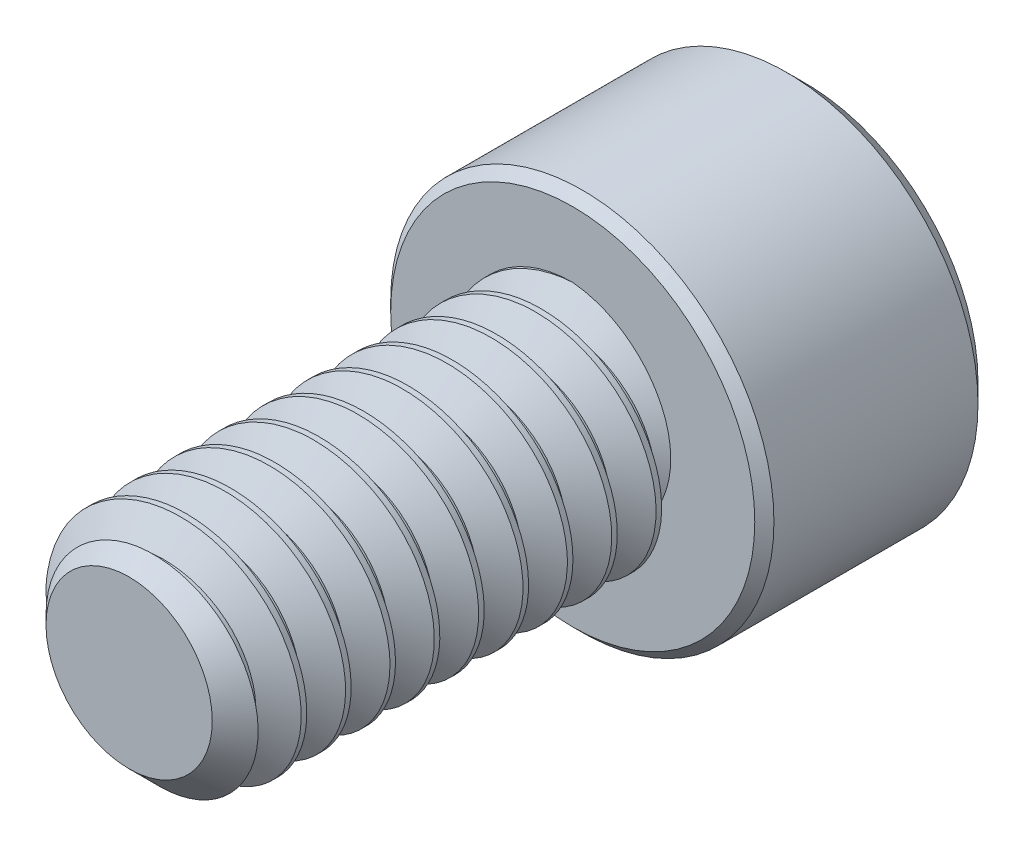
SolidWorks part; units mm, degrees
ref_plane "Front Plane" through (0, 0, 0) normal (0, 0, 1) x (1, 0, 0)
ref_plane "Top Plane" through (0, 0, 0) normal (0, 1, 0) x (1, 0, 0)
ref_plane "Right Plane" through (0, 0, 0) normal (1, 0, 0) x (0, 0, -1)
sketch "Sketch0" plane through (0, 0, 0) normal (1, 0, 0) x (0, 0, -1)
  line L0 (0, 0) -> (7.9375, 0) construction
  point P2 (12.1031, 0)
  point P4 (0, 0)
  dimension "D1" = 7.9375
  dimension "D2" = 4.1656
  dimension "Min Thread" = 0
sketch "Sketch1" plane through (0, 0, 0) normal (0, 0, 1) x (1, 0, 0)
  circle A0 centre (0, 0) radius 2.0828
  dimension "OD" = 4.1656
extrude "Extrude1" add sketch "Sketch1" against normal blind 7.9375
sketch "Sketch2" plane through (0, 0, 0) normal (0, 0, 1) x (1, 0, 0)
  circle A0 centre (0, 0) radius 2.0828 construction
  circle A1 centre (0, 0) radius 2.0828
curve "Helix/Spiral1" pitch 0.7937 height 8.7312 turns 11 parameters "pitch"=0.7937
chamfer "Chamfer3" distance 0.5953 angle 45 1 edges at (2.0828, 0, 0)
sketch "Sketch3" plane through (0, 0, 0) normal (1, 0, 0) x (0, 0, -1)
  line L0 (-0.6945, 2.0828) -> (-0.3969, 1.5672)
  line L1 (-0.3969, 1.5672) -> (-0.2977, 1.5672)
  line L2 (-0.2977, 1.5672) -> (0, 2.0828)
  line L3 (-0.6945, 2.0828) -> (0, 2.0828)
  line L4 (-0.3473, 2.0828) -> (-0.3473, 1.5672) construction
  line L5 (-0.5457, 1.825) -> (-0.1488, 1.825) construction
  line L6 (0, 2.0828) -> (0, -2.0828) construction
  dimension "D1" = 0.0992
  dimension "D2" = 0.3969
  dimension "D3" = 60
sweep "Cut-Sweep1" cut profiles "Sketch3" path "Helix/Spiral1"
sketch "Sketch5" plane through (0, 0, 0) normal (1, 0, 0) x (0, 0, -1)
  line L0 (7.9375, -1.5805) -> (7.9375, 1.4861) construction
  line L1 (7.9375, 2.0828) -> (0, 2.0828)
  line L2 (7.9375, 2.0828) -> (7.9375, 0)
  line L3 (7.9375, 0) -> (-0.7581, 0)
  line L4 (0, 0) -> (7.9375, 0) construction
  line L5 (0, 2.0828) -> (-0.7581, 0)
  line L6 (0, 0) -> (10.4775, 0) construction
  dimension "D1" = 70
  dimension "D3" = 2.54
revolve "partially thread" [suppressed] add sketch "Sketch5" angle 360 about L6
sketch "Sketch6" plane through (0, 0, -7.9375) normal (0, 0, -1) x (-1, 0, 0)
  circle A0 centre (0, 0) radius 3.429
  dimension "head dia" = 6.858
extrude "Extrude2" add sketch "Sketch6" along normal blind 4.1656
sketch "Sketch7" plane through (0, 0, -12.1031) normal (0, 0, -1) x (-1, 0, 0)
  line L1 (0, 2.0622) -> (-1.7859, 1.0311)
  line L2 (-1.7859, 1.0311) -> (-1.7859, -1.0311)
  line L3 (-1.7859, -1.0311) -> (0, -2.0622)
  line L4 (0, -2.0622) -> (1.7859, -1.0311)
  line L5 (1.7859, -1.0311) -> (1.7859, 1.0311)
  line L6 (1.7859, 1.0311) -> (0, 2.0622)
  circle A0 centre (0, 0) radius 1.7859 construction
  dimension "hex dia" = 3.5719
extrude "Cut-Extrude1" cut sketch "Sketch7" against normal blind 2.6789
sketch "Sketch8" plane through (0, 0, -12.1031) normal (0, 0, -1) x (-1, 0, 0)
  circle A0 centre (0, 0) radius 2.0622
extrude "Cut-Extrude2" cut sketch "Sketch8" against normal through all draft 45
chamfer "Chamfer1" distance 0.3429 angle 45 1 edges at (-3.429, 0, -12.1031)
chamfer "Chamfer2" distance 0.1715 angle 45 1 edges at (-3.429, 0, -7.9375)
sketch "Sketch9" plane through (0, 0, 0) normal (1, 0, 0) x (0, 0, -1)
  line L0 (0, 2.0828) -> (0, -2.0828) construction
  line L1 (1.9844, 2.0828) -> (1.9844, -2.0828) construction
  line L2 (12.1031, 3.429) -> (12.1031, -3.429) construction
  line L3 (7.9375, 3.429) -> (7.9375, -3.429) construction
  line L4 (7.9375, 3.2576) -> (7.9375, -3.2576) construction
  line L5 (12.1031, -3.0861) -> (12.1031, 3.0861) construction
  line L6 (7.9375, -3.429) -> (7.9375, 3.429) construction
  line L7 (0, 1.4875) -> (0, -1.4875) construction
  line L8 (-0.6945, 2.0828) -> (0, 2.0828) construction
  line L9 (1.9844, 0) -> (0, 0) construction
  dimension "D1" = 1.9844
equation "\"D3@Helix/Spiral1\" = \"screw length@Extrude1\"+\"pitch@Helix/Spiral1\""
equation "\"D1@Sketch3\" = \"pitch@Helix/Spiral1\"*.125"
equation "\"D2@Sketch3\" = \"pitch@Helix/Spiral1\"*.5"
equation "\"D1@Cut-Extrude1\" = \"hex dia@Sketch7\"*.75"
equation "\"D1@Chamfer1\" = \"head dia@Sketch6\"*.05"
equation "\"D1@Sketch9\" = \"pitch@Helix/Spiral1\"*2.50"
equation "\"D1@Chamfer2\" = \"D1@Chamfer1\"/2"
equation "\"D1@Chamfer3\" = \"pitch@Helix/Spiral1\"*.750"
equation "\"D1@Sketch0\" = \"screw length@Extrude1\""
equation "\"D2@Sketch0\" = \"head depth@Extrude2\""
